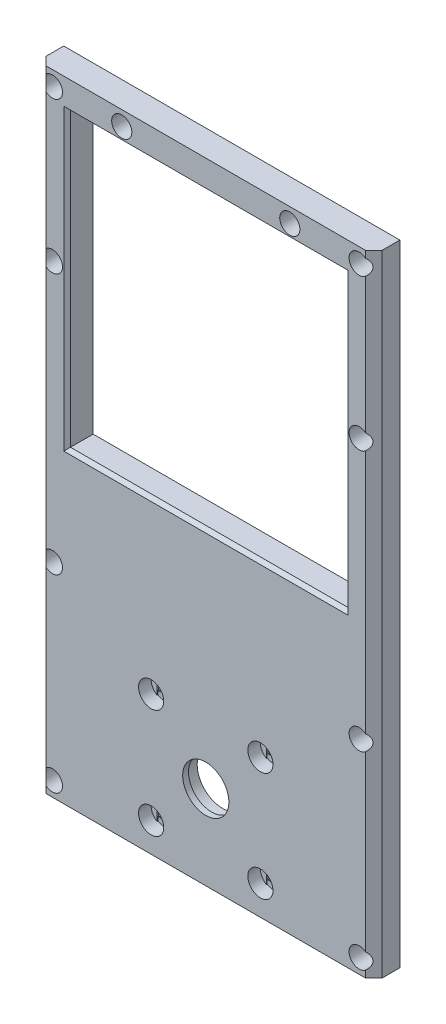
SolidWorks part; units mm, degrees
ref_plane "Front Plane" through (0, 0, 0) normal (0, 0, 1) x (1, 0, 0)
ref_plane "Top Plane" through (0, 0, 0) normal (0, 1, 0) x (1, 0, 0)
ref_plane "Right Plane" through (0, 0, 0) normal (1, 0, 0) x (0, 0, -1)
sketch "Sketch1" plane through (0, 0, 0) normal (0, 0, 1) x (1, 0, 0)
  line L1 (-40, -75) -> (40, -75)
  line L2 (-40, -75) -> (-40, 75)
  line L3 (-40, 75) -> (40, 75)
  line L4 (40, -75) -> (40, 75)
  line L5 (-40, -75) -> (40, 75) construction
  line L6 (-40, 75) -> (40, -75) construction
  line L7 (-33, -68) -> (33, -68)
  line L8 (-33, -68) -> (-33, 68)
  line L9 (-33, 68) -> (33, 68)
  line L10 (33, -68) -> (33, 68)
  line L11 (-33, -68) -> (33, 68) construction
  line L12 (-33, 68) -> (33, -68) construction
  point P0 (0, 0)
  point P6 (0, 0)
  dimension "D1" = 150
  dimension "D2" = 80
  dimension "D3" = 7
  dimension "D4" = 7
extrude "Boss-Extrude1" add sketch "Sketch1" along normal blind 7
sketch "Sketch2" plane through (0, 0, 7) normal (0, 0, 1) x (1, 0, 0)
  line L0 (33, -68) -> (33, 68) construction
  line L1 (-33, -68) -> (33, -68)
  line L2 (-33, -68) -> (-33, -32)
  line L3 (-33, -32) -> (33, -32)
  line L4 (33, -68) -> (33, -32)
  dimension "D1" = 36
extrude "Boss-Extrude2" add sketch "Sketch2" against normal up to surface (7 mm away) up to face at (0, 0, 0)
sketch "Sketch3" plane through (0, 0, 0) normal (0, 0, -1) x (-1, 0, 0)
  line L0 (0, -75) -> (0, -55) construction
  line L1 (40, -75) -> (-40, -75) construction
  circle A0 centre (0, -55) radius 5.5
  dimension "D1" = 11
  dimension "D2" = 20
extrude "Cut-Extrude1" cut sketch "Sketch3" against normal through all
sketch "Sketch4" plane through (0, 0, 0) normal (0, 0, -1) x (-1, 0, 0)
  circle A0 centre (0, -55) radius 6.05
  dimension "D1" = 12.1
extrude "Cut-Extrude2" cut sketch "Sketch4" against normal offset from surface (5.6 mm away) 1.4 up to face at (-5.5, -55, 7)
sketch "Sketch5" plane through (0, 0, 0) normal (0, 0, -1) x (-1, 0, 0)
  circle A0 centre (0, -55) radius 11
  dimension "D1" = 22
extrude "Cut-Extrude3" cut sketch "Sketch5" against normal offset from surface (3 mm away) 2.6 up to face at (-6.05, -55, 5.6)
sketch "Sketch6" plane through (0, 0, 0) normal (0, 0, -1) x (-1, 0, 0)
  line L1 (-13, -68) -> (13, -68) construction
  line L2 (-13, -68) -> (-13, -42) construction
  line L3 (-13, -42) -> (13, -42) construction
  line L4 (13, -68) -> (13, -42) construction
  line L5 (-13, -68) -> (13, -42) construction
  line L6 (-13, -42) -> (13, -68) construction
  circle A0 centre (-13, -42) radius 1.6
  circle A1 centre (13, -42) radius 1.6
  circle A2 centre (13, -68) radius 1.6
  circle A3 centre (-13, -68) radius 1.6
  point P0 (0, -55)
  dimension "D2" = 3.2
  dimension "D1" = 26
extrude "Cut-Extrude4" cut sketch "Sketch6" against normal through all
sketch "Sketch7" plane through (0, 0, 0) normal (0, 0, -1) x (-1, 0, 0)
  line L1 (-25, -74) -> (25, -74)
  line L2 (-25, -74) -> (-25, -36)
  line L3 (-25, -36) -> (25, -36)
  line L4 (25, -74) -> (25, -36)
  line L5 (-25, -74) -> (25, -36) construction
  line L6 (-25, -36) -> (25, -74) construction
  point P0 (0, -55)
  dimension "D1" = 50
  dimension "D2" = 38
extrude "Cut-Extrude5" cut sketch "Sketch7" against normal blind 1
sketch "Sketch8" plane through (0, 0, 7) normal (0, 0, 1) x (1, 0, 0)
  circle A0 centre (-13, -42) radius 3
  circle A1 centre (13, -42) radius 3
  circle A2 centre (13, -68) radius 3
  circle A3 centre (-13, -68) radius 3
  dimension "D1" = 6
extrude "Cut-Extrude6" cut sketch "Sketch8" against normal blind 3
sketch "Sketch9" plane through (0, 0, 7) normal (0, 0, 1) x (1, 0, 0)
  line L0 (-40, 75) -> (-40, -75) construction
  line L1 (-36.5, -71.5) -> (36.5, -71.5) construction
  line L2 (-36.5, -71.5) -> (-36.5, 71.5) construction
  line L3 (-36.5, 71.5) -> (36.5, 71.5) construction
  line L4 (36.5, -71.5) -> (36.5, 71.5) construction
  line L5 (-36.5, -71.5) -> (36.5, 71.5) construction
  line L6 (-36.5, 71.5) -> (36.5, -71.5) construction
  line L7 (40, 75) -> (-40, 75) construction
  circle A0 centre (-36.5, 71.5) radius 1.35
  circle A1 centre (36.5, 71.5) radius 1.35
  circle A4 centre (-36.5, -71.5) radius 1.35
  circle A5 centre (36.5, -71.5) radius 1.35
  circle A6 centre (-36.5, 35.5) radius 1.35
  circle A7 centre (36.5, 35.5) radius 1.35
  circle A8 centre (36.5, -26.5) radius 1.35
  circle A9 centre (-36.5, -26.5) radius 1.35
  point P0 (0, 0)
  dimension "D3" = 2.7
  dimension "D1" = 3.5
  dimension "D2" = 3.5
  dimension "D4" = 45
  dimension "D5" = 36
extrude "Cut-Extrude7" cut sketch "Sketch9" against normal through all
sketch "Sketch10" plane through (0, 0, 7) normal (0, 0, 1) x (1, 0, 0)
  circle A0 centre (-36.5, 71.5) radius 2.4
  circle A1 centre (36.5, 35.5) radius 2.4
  circle A2 centre (-36.5, 35.5) radius 2.4
  circle A3 centre (36.5, 71.5) radius 2.4
  circle A4 centre (-36.5, -71.5) radius 2.4
  circle A5 centre (36.5, -71.5) radius 2.4
  circle A6 centre (-36.5, -26.5) radius 2.4
  circle A7 centre (36.5, -26.5) radius 2.4
  dimension "D1" = 4.8
extrude "Cut-Extrude8" cut sketch "Sketch10" against normal blind 5
chamfer "Chamfer1" distance 2 angle 45 2 edges at (-40, 0, 7) (40, 0, 7)
sketch "Sketch11" plane through (0, 0, 7) normal (0, 0, 1) x (1, 0, 0)
  line L0 (33, -32) -> (33, 68) construction
  line L1 (-33, -32) -> (33, -32)
  line L2 (-33, -32) -> (-33, -1.5)
  line L3 (-33, -1.5) -> (33, -1.5)
  line L4 (33, -32) -> (33, -1.5)
  line L5 (-38, -75) -> (38, -75) construction
  dimension "D1" = 73.5
extrude "Boss-Extrude3" add sketch "Sketch11" against normal up to surface (7 mm away) up to face at (-35.15, -71.5, 0)
sketch "Sketch12" plane through (0, 0, 7) normal (0, 0, 1) x (1, 0, 0)
  line L0 (-36.5, 71.5) -> (36.5, 71.5) construction
  line L1 (-20, 71.5) -> (20, 71.5) construction
  circle A0 centre (-20, 71.5) radius 1.35
  circle A1 centre (20, 71.5) radius 1.35
  circle A2 centre (-36.5, 71.5) radius 1.35 construction
  point P7 (0, 71.5)
  dimension "D1" = 40
extrude "Cut-Extrude9" cut sketch "Sketch12" against normal through all
sketch "Sketch13" plane through (0, 0, 7) normal (0, 0, 1) x (1, 0, 0)
  circle A0 centre (-20, 71.5) radius 2.4
  circle A1 centre (20, 71.5) radius 2.4
  circle A2 centre (-36.5, 71.5) radius 2.4 construction
extrude "Cut-Extrude10" cut sketch "Sketch13" against normal up to surface (5 mm away) up to face at (-34.1, 71.5, 2)
chamfer "Chamfer2" distance 0.8 angle 45 12 edges at (0, -75, 0) (-40, 0, 0) (0, 75, 0) (40, 0, 0) (33, 33.25, 7) (0, 68, 7) (-33, 33.25, 7) (0, -1.5, 7) (-33, 33.25, 0) (0, 68, 0) (33, 33.25, 0) (0, -1.5, 0)
sketch "Sketch14" plane through (0, 0, 2) normal (0, 0, 1) x (1, 0, 0)
  line L2 (-37.85, -28.4843) -> (-37.85, -24.5157)
  line L4 (-35.15, -28.4843) -> (-35.15, -24.5157)
  line L5 (-37.85, -28.4843) -> (-35.15, -24.5157) construction
  line L6 (-37.85, -24.5157) -> (-35.15, -28.4843) construction
  line L14 (-37.85, -73.4843) -> (-37.85, -69.5157)
  line L16 (-35.15, -73.4843) -> (-35.15, -69.5157)
  line L17 (-37.85, -73.4843) -> (-35.15, -69.5157) construction
  line L18 (-37.85, -69.5157) -> (-35.15, -73.4843) construction
  line L26 (-37.85, 33.5157) -> (-37.85, 37.4843)
  line L28 (-35.15, 33.5157) -> (-35.15, 37.4843)
  line L29 (-37.85, 33.5157) -> (-35.15, 37.4843) construction
  line L30 (-37.85, 37.4843) -> (-35.15, 33.5157) construction
  line L32 (-21.35, 69.5157) -> (-21.35, 73.4843)
  line L34 (-18.65, 69.5157) -> (-18.65, 73.4843)
  line L35 (-21.35, 69.5157) -> (-18.65, 73.4843) construction
  line L36 (-21.35, 73.4843) -> (-18.65, 69.5157) construction
  line L38 (-37.85, 69.5157) -> (-37.85, 73.4843)
  line L40 (-35.15, 69.5157) -> (-35.15, 73.4843)
  line L41 (-37.85, 69.5157) -> (-35.15, 73.4843) construction
  line L42 (-37.85, 73.4843) -> (-35.15, 69.5157) construction
  arc A0 (-38, -28.3735) -> (-38, -24.6265) centre (-36.5, -26.5) ccw construction
  circle A2 centre (-36.5, -71.5) radius 2.4 construction
  circle A4 centre (-36.5, 35.5) radius 2.4 construction
  circle A5 centre (-20, 71.5) radius 2.4 construction
  circle A6 centre (-36.5, 71.5) radius 2.4 construction
  circle A7 centre (-36.5, 71.5) radius 1.35 construction
  circle A8 centre (-20, 71.5) radius 1.35 construction
  circle A9 centre (-36.5, 35.5) radius 1.35 construction
  circle A10 centre (-36.5, -26.5) radius 1.35 construction
  circle A12 centre (-36.5, -71.5) radius 1.35 construction
  arc A16 (-21.35, 69.5157) -> (-18.65, 69.5157) centre (-20, 71.5) ccw
  arc A17 (-35.15, 73.4843) -> (-37.85, 73.4843) centre (-36.5, 71.5) ccw
  arc A18 (-35.15, 37.4843) -> (-37.85, 37.4843) centre (-36.5, 35.5) ccw
  arc A20 (-37.85, -28.4843) -> (-35.15, -28.4843) centre (-36.5, -26.5) ccw
  arc A22 (-35.15, -69.5157) -> (-37.85, -69.5157) centre (-36.5, -71.5) ccw
  arc A23 (-37.85, 69.5157) -> (-35.15, 69.5157) centre (-36.5, 71.5) ccw
  arc A24 (-18.65, 73.4843) -> (-21.35, 73.4843) centre (-20, 71.5) ccw
  arc A25 (-37.85, 33.5157) -> (-35.15, 33.5157) centre (-36.5, 35.5) ccw
  arc A26 (-35.15, -24.5157) -> (-37.85, -24.5157) centre (-36.5, -26.5) ccw
  arc A29 (-37.85, -73.4843) -> (-35.15, -73.4843) centre (-36.5, -71.5) ccw
  point P0 (-36.5, -26.5)
  point P17 (-36.5, -71.5)
  point P33 (-36.5, 35.5)
  point P41 (-20, 71.5)
  point P49 (-36.5, 71.5)
extrude "Cut-Extrude11" cut sketch "Sketch14" against normal blind 0.2
sketch "Sketch15" plane through (0, 0, 1.8) normal (0, 0, 1) x (1, 0, 0)
  line L0 (-35.15, -71.5) -> (-35.15, -69.5157) construction
  line L1 (-37.85, -72.85) -> (-35.15, -72.85)
  line L2 (-37.85, -72.85) -> (-37.85, -70.15)
  line L3 (-37.85, -70.15) -> (-35.15, -70.15)
  line L4 (-35.15, -72.85) -> (-35.15, -70.15)
  line L5 (-37.85, -72.85) -> (-35.15, -70.15) construction
  line L6 (-37.85, -70.15) -> (-35.15, -72.85) construction
  line L7 (-35.15, 35.5) -> (-35.15, 37.4843) construction
  line L8 (-37.85, -27.85) -> (-35.15, -27.85)
  line L9 (-37.85, -27.85) -> (-37.85, -25.15)
  line L10 (-37.85, -25.15) -> (-35.15, -25.15)
  line L11 (-35.15, -27.85) -> (-35.15, -25.15)
  line L12 (-37.85, -27.85) -> (-35.15, -25.15) construction
  line L13 (-37.85, -25.15) -> (-35.15, -27.85) construction
  line L14 (-37.85, 34.15) -> (-35.15, 34.15)
  line L15 (-37.85, 34.15) -> (-37.85, 36.85)
  line L16 (-37.85, 36.85) -> (-35.15, 36.85)
  line L17 (-35.15, 34.15) -> (-35.15, 36.85)
  line L18 (-37.85, 34.15) -> (-35.15, 36.85) construction
  line L19 (-37.85, 36.85) -> (-35.15, 34.15) construction
  line L20 (-35.15, 69.5157) -> (-35.15, 73.4843) construction
  line L21 (-37.85, 70.15) -> (-35.15, 70.15)
  line L22 (-37.85, 70.15) -> (-37.85, 72.85)
  line L23 (-37.85, 72.85) -> (-35.15, 72.85)
  line L24 (-35.15, 70.15) -> (-35.15, 72.85)
  line L25 (-37.85, 70.15) -> (-35.15, 72.85) construction
  line L26 (-37.85, 72.85) -> (-35.15, 70.15) construction
  line L27 (-18.65, 69.5157) -> (-18.65, 73.4843) construction
  line L28 (-21.35, 70.15) -> (-18.65, 70.15)
  line L29 (-21.35, 70.15) -> (-21.35, 72.85)
  line L30 (-21.35, 72.85) -> (-18.65, 72.85)
  line L31 (-18.65, 70.15) -> (-18.65, 72.85)
  line L32 (-21.35, 70.15) -> (-18.65, 72.85) construction
  line L33 (-21.35, 72.85) -> (-18.65, 70.15) construction
  arc A0 (-35.15, -26.5) -> (-37.85, -26.5) centre (-36.5, -26.5) ccw construction
  arc A1 (-35.15, 35.5) -> (-37.85, 35.5) centre (-36.5, 35.5) ccw construction
  arc A2 (-18.65, 71.5) -> (-21.35, 71.5) centre (-20, 71.5) ccw construction
  arc A3 (-35.15, 71.5) -> (-37.85, 71.5) centre (-36.5, 71.5) ccw construction
  point P0 (-36.5, -71.5)
  point P8 (-36.5, -26.5)
  point P17 (-36.5, 35.5)
  point P28 (-36.5, 71.5)
  point P36 (-20, 71.5)
extrude "Cut-Extrude12" cut sketch "Sketch15" against normal blind 0.2
sketch "Sketch16" plane through (0, 0, 4) normal (0, 0, 1) x (1, 0, 0)
  line L2 (-14.6, -44.5377) -> (-14.6, -39.4623)
  line L4 (-11.4, -44.5377) -> (-11.4, -39.4623)
  line L5 (-14.6, -44.5377) -> (-11.4, -39.4623) construction
  line L6 (-14.6, -39.4623) -> (-11.4, -44.5377) construction
  line L8 (-14.6, -70.5377) -> (-14.6, -65.4623)
  line L10 (-11.4, -70.5377) -> (-11.4, -65.4623)
  line L11 (-14.6, -70.5377) -> (-11.4, -65.4623) construction
  line L12 (-14.6, -65.4623) -> (-11.4, -70.5377) construction
  circle A0 centre (-13, -42) radius 3 construction
  circle A1 centre (-13, -68) radius 3 construction
  circle A2 centre (-13, -68) radius 1.6 construction
  circle A3 centre (-13, -42) radius 1.6 construction
  circle A4 centre (-13, -68) radius 3 construction
  circle A5 centre (-13, -42) radius 3 construction
  arc A6 (-11.4, -65.4623) -> (-14.6, -65.4623) centre (-13, -68) ccw
  arc A7 (-14.6, -44.5377) -> (-11.4, -44.5377) centre (-13, -42) ccw
  arc A8 (-11.4, -39.4623) -> (-14.6, -39.4623) centre (-13, -42) ccw
  arc A9 (-14.6, -70.5377) -> (-11.4, -70.5377) centre (-13, -68) ccw
  point P0 (-13, -42)
  point P8 (-13, -68)
extrude "Cut-Extrude13" cut sketch "Sketch16" against normal blind 0.2
sketch "Sketch17" plane through (0, 0, 3.8) normal (0, 0, 1) x (1, 0, 0)
  line L0 (-11.4, -44.5377) -> (-11.4, -39.4623) construction
  line L1 (-14.6, -43.6) -> (-11.4, -43.6)
  line L2 (-14.6, -43.6) -> (-14.6, -40.4)
  line L3 (-14.6, -40.4) -> (-11.4, -40.4)
  line L4 (-11.4, -43.6) -> (-11.4, -40.4)
  line L5 (-14.6, -43.6) -> (-11.4, -40.4) construction
  line L6 (-14.6, -40.4) -> (-11.4, -43.6) construction
  line L7 (-11.4, -70.5377) -> (-11.4, -65.4623) construction
  line L8 (-14.6, -69.6) -> (-11.4, -69.6)
  line L9 (-14.6, -69.6) -> (-14.6, -66.4)
  line L10 (-14.6, -66.4) -> (-11.4, -66.4)
  line L11 (-11.4, -69.6) -> (-11.4, -66.4)
  line L12 (-14.6, -69.6) -> (-11.4, -66.4) construction
  line L13 (-14.6, -66.4) -> (-11.4, -69.6) construction
  arc A0 (-11.4, -68) -> (-14.6, -68) centre (-13, -68) ccw construction
  arc A1 (-11.4, -42) -> (-14.6, -42) centre (-13, -42) ccw construction
  point P0 (-13, -42)
  point P8 (-13, -68)
extrude "Cut-Extrude14" cut sketch "Sketch17" against normal blind 0.2
mirror "Mirror1" about plane through (0, 0, 0) normal (1, 0, 0) of "Cut-Extrude12", "Cut-Extrude13", "Cut-Extrude14", "Cut-Extrude11"
